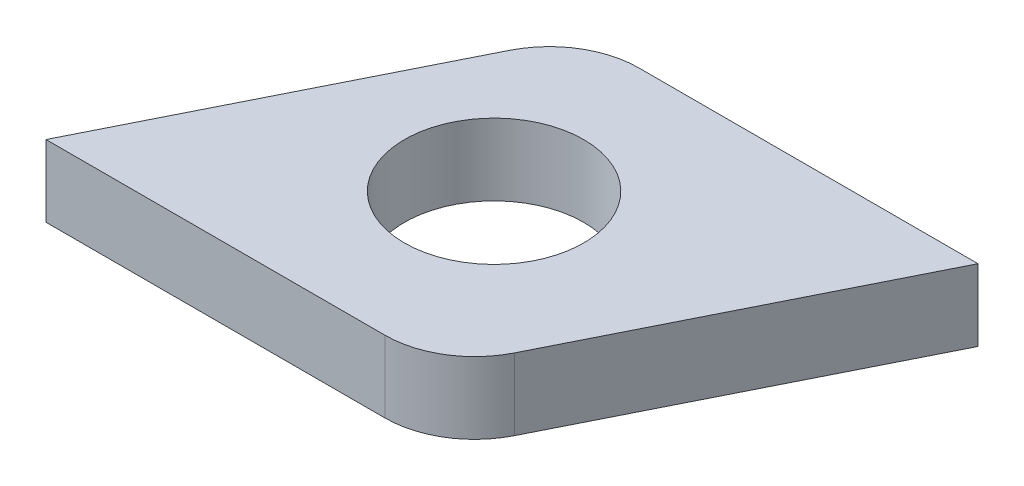
SolidWorks part; units mm, degrees
ref_plane "Спереди" through (0, 0, 0) normal (0, 0, 1) x (1, 0, 0)
ref_plane "Сверху" through (0, 0, 0) normal (0, 1, 0) x (1, 0, 0)
ref_plane "Справа" through (0, 0, 0) normal (1, 0, 0) x (0, 0, -1)
sketch "Эскиз1" plane through (0, 0, 0) normal (0, 1, 0) x (1, 0, 0)
  line L0 (0, 0) -> (18.9098, 0)
  line L1 (23.382, 2.7639) -> (32, 20)
  line L2 (32, 20) -> (13.0902, 20)
  line L3 (8.618, 17.2361) -> (0, 0)
  arc A0 (18.9098, 0) -> (23.382, 2.7639) centre (18.9098, 5) ccw
  arc A1 (13.0902, 20) -> (8.618, 17.2361) centre (13.0902, 15) ccw
  dimension "D1" = 5
extrude "Бобышка-Вытянуть1" add sketch "Эскиз1" along normal blind 4
sketch "Эскиз2" plane through (0, 4, 0) normal (0, 1, 0) x (1, 0, 0)
  circle A0 centre (15, 10) radius 5
extrude "Вырез-Вытянуть1" cut sketch "Эскиз2" against normal through all
